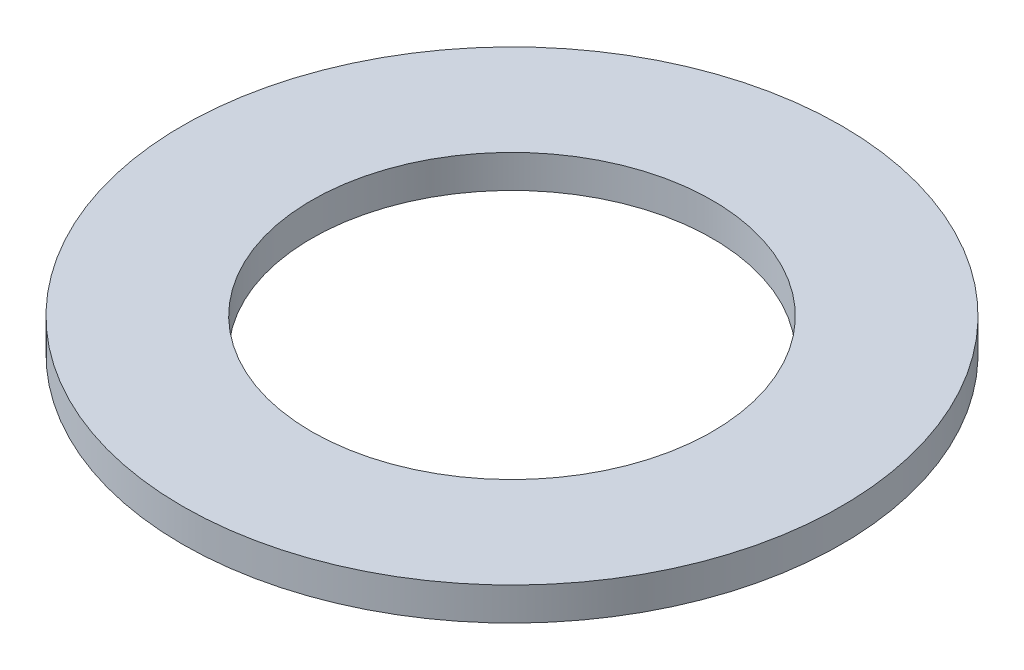
SolidWorks part; units mm, degrees
material "PET"
ref_plane "Front Plane" through (0, 0, 0) normal (0, 0, 1) x (1, 0, 0)
ref_plane "Top Plane" through (0, 0, 0) normal (0, 1, 0) x (1, 0, 0)
ref_plane "Right Plane" through (0, 0, 0) normal (1, 0, 0) x (0, 0, -1)
sketch "Sketch1" plane through (0, 0, 0) normal (0, 1, 0) x (1, 0, 0)
  circle A0 centre (0, 0) radius 7.9375
  circle A1 centre (0, 0) radius 4.826
  dimension "D1" = 9.652
  dimension "D2" = 15.875
extrude "Boss-Extrude1" add sketch "Sketch1" along normal blind 0.7937
